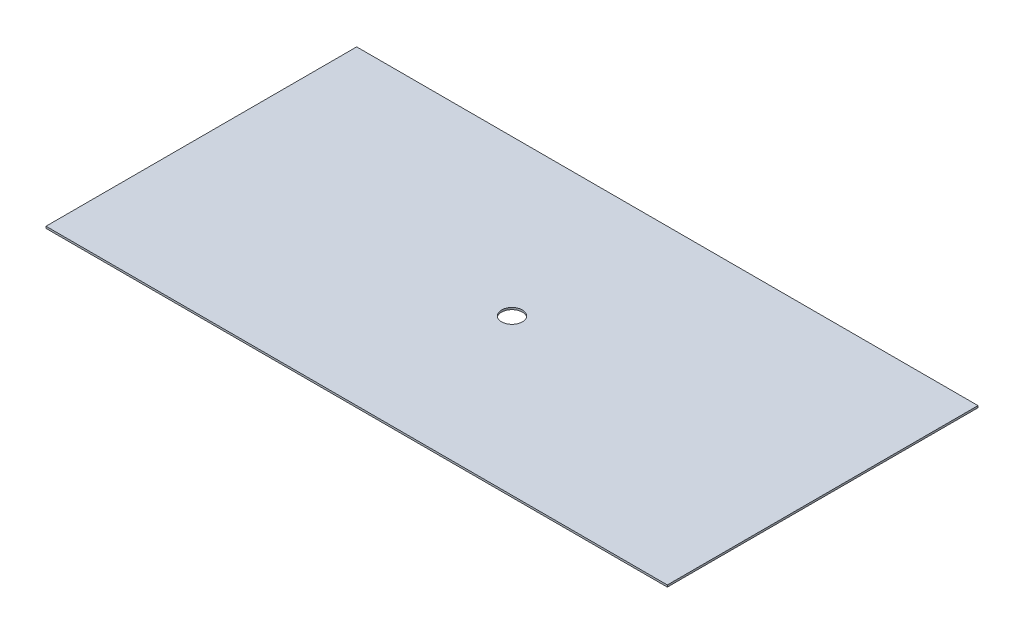
SolidWorks part; units mm, degrees
ref_plane "Front Plane" through (0, 0, 0) normal (0, 0, 1) x (1, 0, 0)
ref_plane "Top Plane" through (0, 0, 0) normal (0, 1, 0) x (1, 0, 0)
ref_plane "Right Plane" through (0, 0, 0) normal (1, 0, 0) x (0, 0, -1)
sketch "Sketch1" plane through (0, 0, 0) normal (0, 1, 0) x (1, 0, 0)
  line L1 (-120, 60) -> (120, 60)
  line L2 (-120, 60) -> (-120, -60)
  line L3 (-120, -60) -> (120, -60)
  line L4 (120, 60) -> (120, -60)
  dimension "D1" = 120
  dimension "D2" = 240
  dimension "D3" = 60
  dimension "D4" = 120
base flange "Base-Flange1" sketch "Sketch1" thickness 0.7366 reverse thickness direction no parameters "D1"=0.7366
hole_wizard "Ø4.0 (4) Diameter Hole1" positions "Sketch7" profile "Sketch6" hole size "Ø4.0" standard "ISO" end condition through all
sketch "Sketch7" plane through (0, 0, 0) normal (0, 1, 0) x (1, 0, 0)
  point P0 (0, 0)
sketch "Sketch6" plane through (0, 0, 0) normal (1, 0, 0) x (0, 0, 1)
  line L0 (0, 0) -> (0, 0.7366)
  line L1 (0, 0.7366) -> (4, 0.7366)
  line L2 (4, 0.7366) -> (4, 0)
  line L5 (4, 0) -> (0, 0)
  line L11 (0, -6.35) -> (0, 107.95) construction
  dimension "Thru Hole Dia." = 8
  dimension "Thru Hole Depth" = 0.7366
sketch "Sketch8" plane through (0, 0, 0) normal (0, 1, 0) x (1, 0, 0)
sketch "Bend-Lines1" plane through (0, 0, 0) normal (0, 1, 0) x (1, 0, 0)
sketch "Bounding-Box1" plane through (0, 0, 0) normal (0, 1, 0) x (1, 0, 0)
sheet metal parameters "Sheet-Metal1" thickness 0.7366 parameters "D1"=0.7366
flat pattern "Flat-Pattern1" [suppressed]
sketch "Bend-Lines2" plane through (0, 0, 0) normal (0, 1, 0) x (1, 0, 0)
sketch "Bounding-Box2" [suppressed] plane through (0, 0, 0) normal (0, 1, 0) x (1, 0, 0)
sheet metal parameters "Sheet-Metal2" thickness 0.7366 parameters "D1"=0.7366
flat pattern "Flat-Pattern1"
sketch "Bend-Lines2" plane through (0, 0, 0) normal (0, 1, 0) x (1, 0, 0)
sketch "Bounding-Box2" [suppressed] plane through (0, 0, 0) normal (0, 1, 0) x (1, 0, 0)
